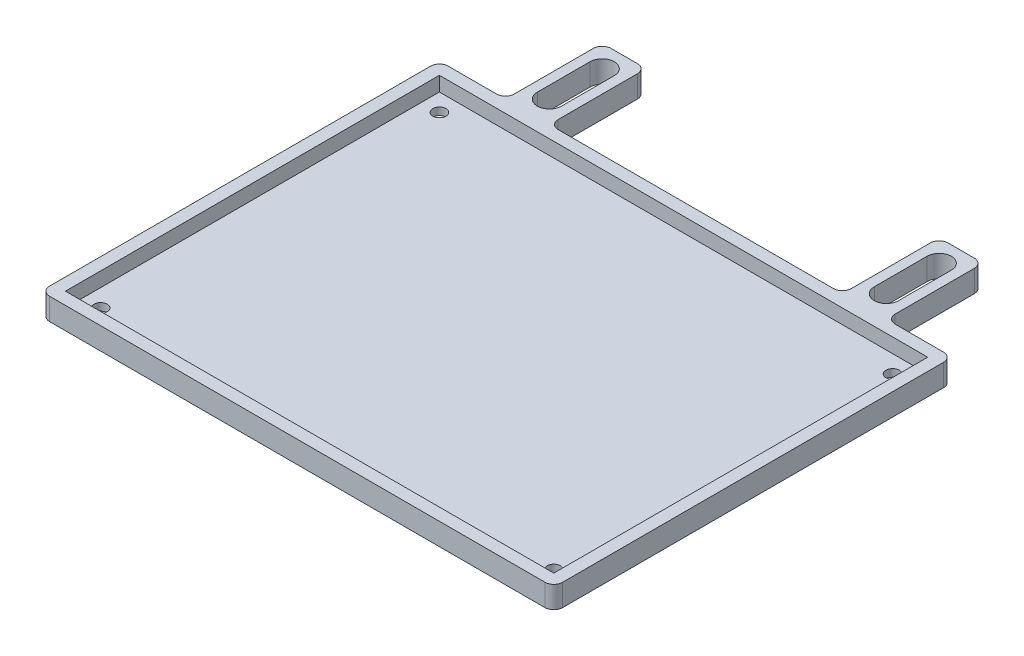
SolidWorks part; units mm, degrees
ref_plane "前视基准面" through (0, 0, 0) normal (0, 0, 1) x (1, 0, 0)
ref_plane "上视基准面" through (0, 0, 0) normal (0, 1, 0) x (1, 0, 0)
ref_plane "右视基准面" through (0, 0, 0) normal (1, 0, 0) x (0, 0, -1)
sketch "草图2" plane through (0, 0, 0) normal (0, 1, 0) x (1, 0, 0)
  line L0 (-43.3, 45.3) -> (-43.3, 67.3)
  line L1 (58.3, 45.3) -> (43.3, 45.3)
  line L2 (58.3, 45.3) -> (58.3, -45.3)
  line L3 (58.3, -45.3) -> (-58.3, -45.3)
  line L4 (-58.3, 45.3) -> (-58.3, -45.3)
  line L5 (58.3, 45.3) -> (-58.3, -45.3) construction
  line L6 (58.3, -45.3) -> (-58.3, 45.3) construction
  line L7 (-43.3, 67.3) -> (-33.3, 67.3)
  line L8 (-33.3, 67.3) -> (-33.3, 45.3)
  line L9 (-43.3, 45.3) -> (-58.3, 45.3)
  line L10 (0, 25.3734) -> (0, -22.0387) construction
  line L11 (33.3, 67.3) -> (33.3, 45.3)
  line L12 (43.3, 67.3) -> (33.3, 67.3)
  line L13 (43.3, 45.3) -> (43.3, 67.3)
  line L14 (33.3, 45.3) -> (-33.3, 45.3)
  line L15 (-38.3, 62.3) -> (-38.3, 50.3) construction
  line L16 (-35.55, 62.3) -> (-35.55, 50.3)
  line L17 (-41.05, 62.3) -> (-41.05, 50.3)
  line L18 (38.3, 62.3) -> (38.3, 50.3) construction
  line L19 (35.55, 62.3) -> (35.55, 50.3)
  line L20 (41.05, 62.3) -> (41.05, 50.3)
  arc A0 (-35.55, 62.3) -> (-41.05, 62.3) centre (-38.3, 62.3) ccw
  arc A1 (-41.05, 50.3) -> (-35.55, 50.3) centre (-38.3, 50.3) ccw
  arc A2 (35.55, 62.3) -> (41.05, 62.3) centre (38.3, 62.3) cw
  arc A3 (41.05, 50.3) -> (35.55, 50.3) centre (38.3, 50.3) cw
  point P0 (0, 0)
  point P8 (-43.3, 56.3)
  point P19 (-38.3, 56.3)
  point P26 (38.3, 56.3)
  dimension "D1" = 116.6
  dimension "D2" = 90.6
  dimension "D3" = 15
  dimension "D4" = 10
  dimension "D5" = 22
  dimension "D6" = 5.5
  dimension "D7" = 5
  dimension "D8" = 11
  dimension "D9" = 12
extrude "凸台-拉伸1" add sketch "草图2" along normal blind 5
sketch "草图4" plane through (0, 5, 0) normal (0, 1, 0) x (1, 0, 0)
  line L0 (-55.5, -42.5) -> (55.5, 42.5) construction
  line L1 (55.5, 42.5) -> (-55.5, 42.5)
  line L2 (55.5, 42.5) -> (55.5, -42.5)
  line L3 (55.5, -42.5) -> (-55.5, -42.5)
  line L4 (-55.5, 42.5) -> (-55.5, -42.5)
  line L5 (-55.5, 42.5) -> (55.5, -42.5) construction
  line L7 (0, 17.7593) -> (0, -21.0825) construction
  line L8 (-11.7709, 0) -> (12.9609, 0) construction
  circle A0 centre (-51.5, 38.5) radius 1.5
  circle A1 centre (-51.5, -38.5) radius 1.5
  circle A2 centre (51.5, -38.5) radius 1.5
  circle A3 centre (51.5, 38.5) radius 1.5
  point P0 (0, 0)
  dimension "D3" = 4
  dimension "D1" = 42.5
  dimension "D2" = 55.5
  dimension "D4" = 4
  dimension "D5" = 55.5
  dimension "D6" = 42.5
extrude "切除-拉伸4" cut sketch "草图4" against normal through all contours A0 | A1 | A2 | A3 region at (-51.5, 5, -38.5) region at (-51.5, 5, 38.5) region at (51.5, 5, 38.5) region at (51.5, 5, -38.5)
extrude "切除-拉伸5" cut sketch "草图4<3>" against normal blind 3.3 contours L1 L4 L3 L2 A1 A0 A2 A3 region at (0, 5, 0)
sketch "草图4<3>" plane through (0, 5, 0) normal (0, 1, 0) x (1, 0, 0) same geometry as "草图4"
fillet "圆角1" radius 2 12 edges at (58.3, 2.5, 45.3) (-58.3, 2.5, 45.3) (-58.3, 2.5, -45.3) (-43.3, 2.5, -45.3) (-43.3, 2.5, -67.3) (-33.3, 2.5, -67.3) (-33.3, 2.5, -45.3) (33.3, 2.5, -45.3) (33.3, 2.5, -67.3) (43.3, 2.5, -67.3) (43.3, 2.5, -45.3) (58.3, 2.5, -45.3)
